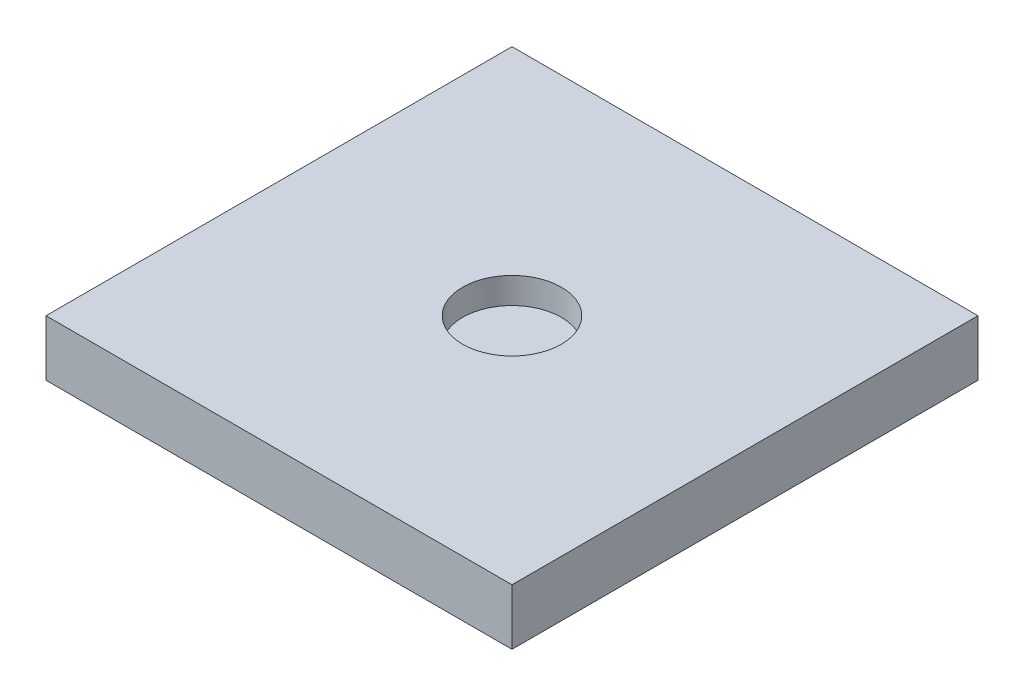
SolidWorks part; units mm, degrees
material "Pine"
ref_plane "Front Plane" through (0, 0, 0) normal (0, 0, 1) x (1, 0, 0)
ref_plane "Top Plane" through (0, 0, 0) normal (0, 1, 0) x (1, 0, 0)
ref_plane "Right Plane" through (0, 0, 0) normal (1, 0, 0) x (0, 0, -1)
sketch "Sketch1" plane through (0, 0, 0) normal (0, 1, 0) x (1, 0, 0)
  line L1 (-62.5, -62.5) -> (62.5, -62.5)
  line L2 (-62.5, -62.5) -> (-62.5, 62.5)
  line L3 (-62.5, 62.5) -> (62.5, 62.5)
  line L4 (62.5, -62.5) -> (62.5, 62.5)
  line L5 (-62.5, -62.5) -> (62.5, 62.5) construction
  line L6 (-62.5, 62.5) -> (62.5, -62.5) construction
  circle A0 centre (0, 0) radius 13.25
  point P0 (0, 0)
  dimension "D1" = 26.5
  dimension "D2" = 125
extrude "Boss-Extrude1" add sketch "Sketch1" along normal blind 15
sketch "Sketch2" plane through (0, 0, 0) normal (0, -1, 0) x (1, 0, 0)
  circle A0 centre (0, 0) radius 13.25 construction
  circle A1 centre (0, 0) radius 13.25
extrude "Boss-Extrude2" add sketch "Sketch2" against normal blind 8
